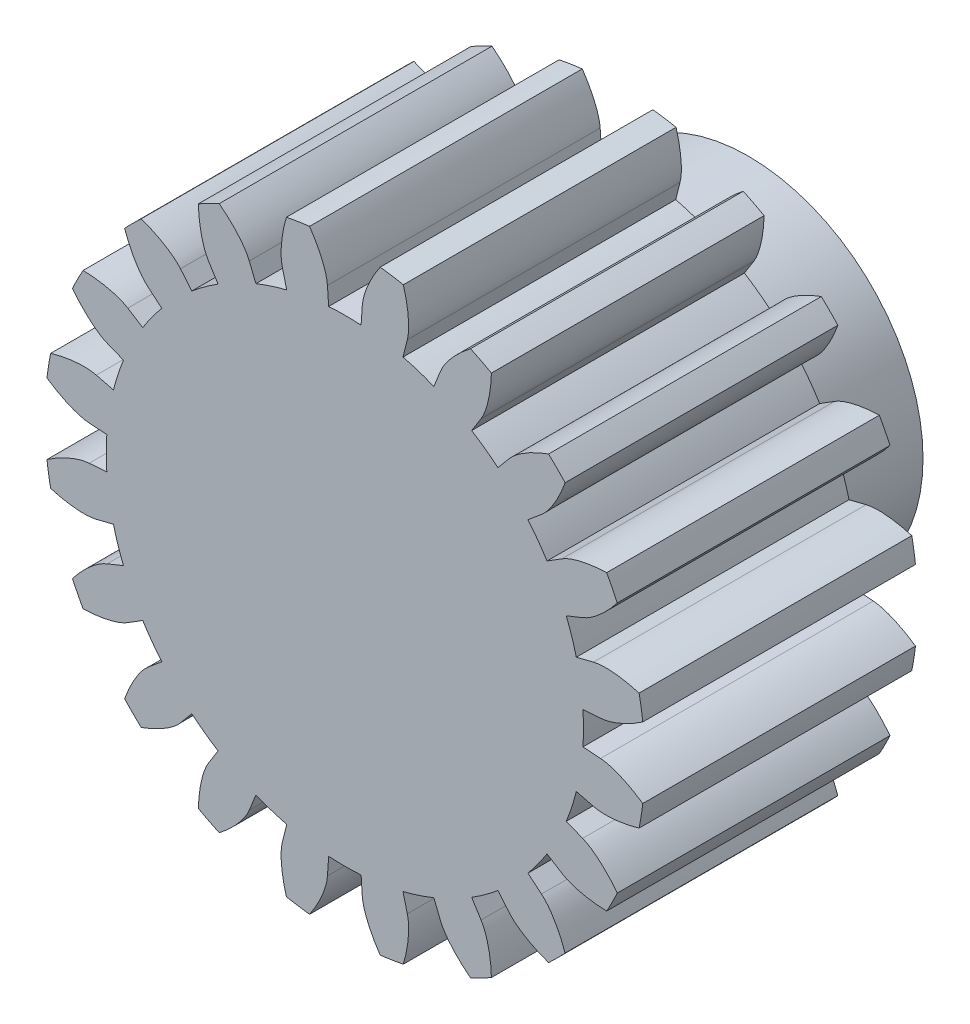
SolidWorks part; units mm, degrees
ref_plane "前视基准面" through (0, 0, 0) normal (0, 0, 1) x (1, 0, 0)
ref_plane "上视基准面" through (0, 0, 0) normal (0, 1, 0) x (1, 0, 0)
ref_plane "右视基准面" through (0, 0, 0) normal (1, 0, 0) x (0, 0, -1)
other "Configuration Table"
sketch "草图1" plane through (0, 0, 0) normal (0, 0, 1) x (1, 0, 0)
  line L0 (0, 0) -> (5, 0) construction
  line L1 (0, 0) -> (4.9846, 0.3923) construction
  line L2 (0, 0) -> (4.6876, 0.3194)
  line L3 (4.9846, 0.3923) -> (4.9846, -0.3923) construction
  line L4 (0, 0) -> (4.6876, -0.3194)
  circle A0 centre (0, 0) radius 5.5
  circle A1 centre (0, 0) radius 5 construction
  circle A2 centre (0, 0) radius 4.375
  circle A3 centre (0, 0) radius 4.6985 construction
  circle A4 centre (0, 0) radius 1.475
  spline S0 degree 4 poles (4.6876, 0.3194) (4.7233, 0.3218) (4.8225, 0.336) (5.0062, 0.3926) (5.2885, 0.5242) (5.6241, 0.7499) (6.0094, 1.0976) (6.395, 1.5688) (6.7398, 2.1414) (7.0933, 2.9696) (7.3065, 3.8467) (7.3947, 4.7795) (7.347, 5.8934) (7.1568, 6.9938) (6.7515, 8.227) (6.0949, 9.5107) (5.2611, 10.6861) (4.2765, 11.7378) (3.1662, 12.6551) (1.9531, 13.4307) (0.6586, 14.0604) (-0.5283, 14.4821) (-1.4854, 14.7287) (-2.1912, 14.8654) (-2.6338, 14.9356) (-2.9917, 14.9827) (-3.3451, 15.0208) (-3.7095, 15.05) (-4.0266, 15.0684) (-4.3306, 15.0786) (-4.6986, 15.0842) (-4.9527, 15.0816) (-5.4001, 15.0704) (-5.6957, 15.0494) (-6.0237, 15.027) (-6.2862, 14.9991) (-6.5922, 14.9657) (-6.7961, 14.9366) (-6.9439, 14.9154) (-7.0152, 14.9043) knots 0 0 0 0 0 0.005604 0.015718 0.02996 0.048734 0.068727 0.096889 0.125051 0.153212 0.209535 0.237696 0.271429 0.327752 0.384075 0.440398 0.496721 0.553044 0.609367 0.66569 0.722013 0.778336 0.806497 0.820578 0.834659 0.84874 0.86282 0.876901 0.890982 0.900036 0.909091 0.931818 0.943182 0.954545 0.965909 0.977273 0.988636 1 1 1 1 1 construction
  spline S1 degree 4 poles (4.6876, 0.3194) (4.7233, 0.3218) (4.8225, 0.336) (5.0062, 0.3926) (5.2885, 0.5242) (5.6241, 0.7499) (6.0094, 1.0976) (6.395, 1.5688) (6.7398, 2.1414) (7.0933, 2.9696) (7.3065, 3.8467) (7.3947, 4.7795) (7.347, 5.8934) (7.1568, 6.9938) (6.7515, 8.227) (6.0949, 9.5107) (5.2611, 10.6861) (4.2765, 11.7378) (3.1662, 12.6551) (1.9531, 13.4307) (0.6586, 14.0604) (-0.5283, 14.4821) (-1.4854, 14.7287) (-2.1912, 14.8654) (-2.6338, 14.9356) (-2.9917, 14.9827) (-3.3451, 15.0208) (-3.7095, 15.05) (-4.0266, 15.0684) (-4.3306, 15.0786) (-4.5463, 15.0819) (-4.6529, 15.0825) (-4.7054, 15.0825) knots 0 0 0 0 0 0.005604 0.015718 0.02996 0.048734 0.068727 0.096889 0.125051 0.153212 0.209535 0.237696 0.271429 0.327752 0.384075 0.440398 0.496721 0.553044 0.609367 0.66569 0.722013 0.778336 0.806497 0.820578 0.834659 0.84874 0.86282 0.876901 0.890982 0.900036 0.909091 0.909091 0.909091 0.909091 0.909091
  spline S2 degree 4 poles (4.6876, -0.3194) (4.7233, -0.3218) (4.8225, -0.336) (5.0062, -0.3926) (5.2885, -0.5242) (5.6241, -0.7499) (6.0094, -1.0976) (6.395, -1.5688) (6.7398, -2.1414) (7.0933, -2.9696) (7.3065, -3.8467) (7.3947, -4.7795) (7.347, -5.8934) (7.1568, -6.9938) (6.7515, -8.227) (6.0949, -9.5107) (5.2611, -10.6861) (4.2765, -11.7378) (3.1662, -12.6551) (1.9531, -13.4307) (0.6586, -14.0604) (-0.5283, -14.4821) (-1.4854, -14.7287) (-2.1912, -14.8654) (-2.6338, -14.9356) (-2.9917, -14.9827) (-3.3451, -15.0208) (-3.7095, -15.05) (-4.0266, -15.0684) (-4.3306, -15.0786) (-4.6986, -15.0842) (-4.9527, -15.0816) (-5.4001, -15.0704) (-5.6957, -15.0494) (-6.0237, -15.027) (-6.2862, -14.9991) (-6.5922, -14.9657) (-6.7961, -14.9366) (-6.9439, -14.9154) (-7.0152, -14.9043) knots 0 0 0 0 0 0.005604 0.015718 0.02996 0.048734 0.068727 0.096889 0.125051 0.153212 0.209535 0.237696 0.271429 0.327752 0.384075 0.440398 0.496721 0.553044 0.609367 0.66569 0.722013 0.778336 0.806497 0.820578 0.834659 0.84874 0.86282 0.876901 0.890982 0.900036 0.909091 0.931818 0.943182 0.954545 0.965909 0.977273 0.988636 1 1 1 1 1 construction
  spline S3 degree 4 poles (4.6876, -0.3194) (4.7233, -0.3218) (4.8225, -0.336) (5.0062, -0.3926) (5.2885, -0.5242) (5.6241, -0.7499) (6.0094, -1.0976) (6.395, -1.5688) (6.7398, -2.1414) (7.0933, -2.9696) (7.3065, -3.8467) (7.3947, -4.7795) (7.347, -5.8934) (7.1568, -6.9938) (6.7515, -8.227) (6.0949, -9.5107) (5.2611, -10.6861) (4.2765, -11.7378) (3.1662, -12.6551) (1.9531, -13.4307) (0.6586, -14.0604) (-0.5283, -14.4821) (-1.4854, -14.7287) (-2.1912, -14.8654) (-2.6338, -14.9356) (-2.9917, -14.9827) (-3.3451, -15.0208) (-3.7095, -15.05) (-4.0266, -15.0684) (-4.3306, -15.0786) (-4.5463, -15.0819) (-4.6529, -15.0825) (-4.7054, -15.0825) knots 0 0 0 0 0 0.005604 0.015718 0.02996 0.048734 0.068727 0.096889 0.125051 0.153212 0.209535 0.237696 0.271429 0.327752 0.384075 0.440398 0.496721 0.553044 0.609367 0.66569 0.722013 0.778336 0.806497 0.820578 0.834659 0.84874 0.86282 0.876901 0.890982 0.900036 0.909091 0.909091 0.909091 0.909091 0.909091
  point P15 (4.9846, 0)
  dimension "齿顶圆直径" = 11
  dimension "分度圆直径" = 10
  dimension "齿根圆直径" = 8.75
  dimension "基圆直径" = 9.3969
  dimension "内孔直径" = 2.95
  dimension "渐近线镜像线夹角" = 4.5
extrude "凸台-拉伸1" add sketch "草图1" along normal blind 5 contours A0 | A4
extrude "切除-拉伸1" cut sketch "草图1<3>" along normal through all contours A2 S3 A0 S1 region at (5.0102, 0, 0)
sketch "草图1<3>" plane through (0, 0, 0) normal (0, 0, 1) x (1, 0, 0) same geometry as "草图1"
pattern_circular "阵列(圆周)1" count 20 every 18 about axis through (0, 0, 5) along (0, 0, 1) of "切除-拉伸1"
sketch "草图2" plane through (0, 0, 5) normal (0, 0, 1) x (1, 0, 0)
  circle A0 centre (0, 0) radius 1.475
extrude "凸台-拉伸2" add sketch "草图2" against normal through all
sketch "草图3" plane through (0, 0, 0) normal (0, 0, -1) x (-1, 0, 0)
  line L1 (0.6, 1.0392) -> (-0.6, 1.0392)
  line L2 (-0.6, 1.0392) -> (-1.2, 0)
  line L3 (-1.2, 0) -> (-0.6, -1.0392)
  line L4 (-0.6, -1.0392) -> (0.6, -1.0392)
  line L5 (0.6, -1.0392) -> (1.2, 0)
  line L6 (1.2, 0) -> (0.6, 1.0392)
  circle A0 centre (0, 0) radius 2.2
  circle A1 centre (0, 0) radius 3.2
  circle A2 centre (0, 0) radius 1.0392 construction
  dimension "D1" = 1
  dimension "D2" = 4.4
  dimension "D3" = 1.2
extrude "凸台-拉伸3" add sketch "草图3" along normal blind 2.4 contours A1 A0 | L5 L6 L1 L2 L3 L4 region at (0, 0, 0) region at (3.1095, 0, 0)
sketch "草图4" plane through (0, 0, 5) normal (0, 0, 1) x (1, 0, 0)
  line L0 (1, 1.118) -> (1, -1.118)
  circle A0 centre (0, 0) radius 1.5
  dimension "D1" = 3
  dimension "D2" = 1
sketch "草图5" plane through (0, 0, -2.4) normal (0, 0, -1) x (-1, 0, 0)
  circle A0 centre (0, 0) radius 1.2
extrude "切除-拉伸2" cut sketch "草图5" against normal blind 1
equation "\"m\"= 0.5'模数"
equation "\"z\"= 20'齿数"
equation "\"a\"= 20度'压力角"
equation "\"d\"= \"m\" * \"z\"'分度圆直径"
equation "\"da\"= ( \"z\" + 2 ) * \"m\"'齿顶圆直径"
equation "\"df\"= ( \"z\" - 2.5 ) * \"m\"'齿根圆直径"
equation "\"s\"= 0.5 * PI * \"m\"'分度圆齿厚"
equation "\"r\"= 0.38 * \"m\"'齿根圆角"
equation "\"B\"= 0.3 * \"d\"'齿厚"
equation "\"db\"= \"m\" * \"z\" * cos ( \"a\" )'基圆直径"
equation "\"rb\"= \"db\" / 2'基圆半径"
equation "\"齿顶圆直径@草图1\"= \"da\""
equation "\"分度圆直径@草图1\"= \"d\""
equation "\"齿根圆直径@草图1\"= \"df\""
equation "\"基圆直径@草图1\"= \"db\""
equation "\"渐近线镜像线夹角@草图1\"= 360 / 4 / \"z\""
equation "\"h\"= 5'齿轮厚度"
equation "\"ir\"= 2.95'内孔直径"
equation "\"内孔直径@草图1\"= \"ir\""
equation "\"齿轮厚@凸台-拉伸1\"= \"h\""
equation "\"齿轮夹角@阵列(圆周)1\"= 360 / \"z\""
equation "\"齿数@阵列(圆周)1\"= \"z\""
